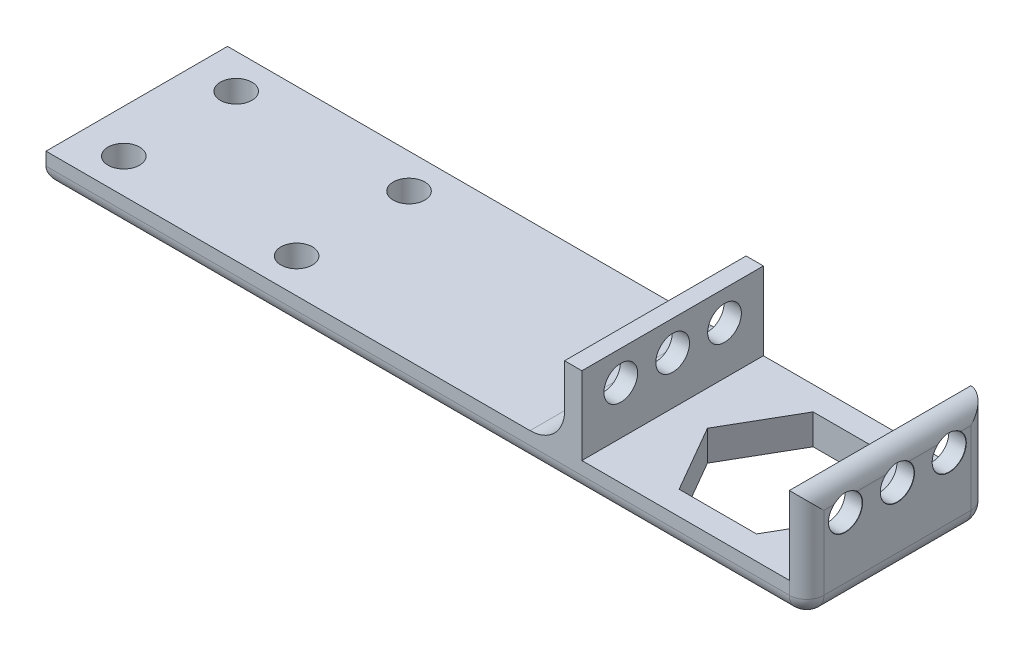
SolidWorks part; units mm, degrees
ref_plane "Front Plane" through (0, 0, 0) normal (0, 0, 1) x (1, 0, 0)
ref_plane "Top Plane" through (0, 0, 0) normal (0, 1, 0) x (1, 0, 0)
ref_plane "Right Plane" through (0, 0, 0) normal (1, 0, 0) x (0, 0, -1)
sketch "Sketch1" plane through (0, 0, 0) normal (0, 0, 1) x (1, 0, 0)
  line L1 (12, 5.0615) -> (12, -23.0615) construction
  line L2 (12, -20.5454) -> (14, -20.5454)
  line L3 (12, -20.5454) -> (12, -29.5454)
  line L5 (14, -20.5454) -> (14, -33.0454)
  line L6 (-12, -23.0615) -> (-12, 5.0615) construction
  line L7 (12, -29.5454) -> (-12, -29.5454)
  line L12 (-14, -29.5454) -> (-14, -20.5454)
  line L13 (-14, -20.5454) -> (-12, -20.5454)
  line L14 (-12, -29.5454) -> (-12, -20.5454)
  line L16 (14, -33.0454) -> (-74, -33.0454)
  line L18 (-14, -29.5454) -> (-74, -29.5454)
  line L19 (-74, -33.0454) -> (-74, -29.5454)
  dimension "D1" = 3.5
  dimension "D2" = 2
  dimension "D3" = 2
  dimension "D4" = 60
  dimension "D5" = 9
extrude "Boss-Extrude1" add sketch "Sketch1" against normal blind 21
fillet "Fillet1" radius 4 1 edges at (-14, -29.5454, -10.5)
hole_wizard "M3.5 Clearance Hole1" positions "Sketch2" profile "Sketch3" hole size "M3.5" standard "ANSI Metric" end condition through all
sketch "Sketch2" plane through (14, 0, 0) normal (1, 0, 0) x (0, 0, -1)
  arc A0 (2.5, -24) -> (6.5, -24) centre (4.5, -24) ccw construction
  arc A1 (2.5, -24) -> (6.5, -24) centre (4.5, -24) ccw construction
  arc A2 (8, -24) -> (13, -24) centre (10.5, -24) ccw construction
  arc A3 (8, -24) -> (13, -24) centre (10.5, -24) ccw construction
  arc A4 (8, -24) -> (13, -24) centre (10.5, -24) ccw construction
  arc A5 (8, -24) -> (13, -24) centre (10.5, -24) ccw construction
  arc A6 (14, -24) -> (19, -24) centre (16.5, -24) ccw construction
  arc A7 (14, -24) -> (19, -24) centre (16.5, -24) ccw construction
  point P0 (4.5, -24)
  point P2 (10.5, -24)
  point P4 (16.5, -24)
sketch "Sketch3" plane through (14, -24, -4.5) normal (0, 1, 0) x (0, 0, -1)
  line L0 (0, 0) -> (0, 88)
  line L1 (0, 88) -> (1.95, 88)
  line L2 (1.95, 88) -> (1.95, 0.025)
  line L3 (1.95, 0.025) -> (1.975, 0)
  line L5 (1.975, 0) -> (0, 0)
  line L6 (-1.95, 0.025) -> (-1.975, 0) construction
  line L11 (0, -6.35) -> (0, 107.95) construction
  dimension "Thru Hole Dia." = 3.9
  dimension "Thru Hole Depth" = 88
  dimension "Near C'Sink Dia." = 3.95
  dimension "Near C'Sink Angle" = 90
sketch "Sketch4" plane through (0, -33.0454, 0) normal (0, -1, 0) x (1, 0, 0)
  line L0 (14, -21) -> (14, 0) construction
  line L5 (-74, 0) -> (14, 0) construction
  line L6 (14, -10.5) -> (-74, -10.5) construction
  line L7 (-74, -21) -> (-74, 0) construction
  line L8 (-3.4992, -18.2528) -> (5.4529, -18.2528)
  line L9 (5.4529, -18.2528) -> (9.929, -10.5)
  line L10 (9.929, -10.5) -> (5.4529, -2.7472)
  line L11 (5.4529, -2.7472) -> (-3.4992, -2.7472)
  line L12 (-3.4992, -2.7472) -> (-7.9753, -10.5)
  line L13 (-7.9753, -10.5) -> (-3.4992, -18.2528)
  circle A0 centre (0.9769, -10.5) radius 7.7528 construction
  circle A1 centre (-69, -4) radius 1.825
  circle A2 centre (-49, -4) radius 1.825
  circle A3 centre (18.1662, -42.7784) radius 1.825
  circle A4 centre (28.1662, -60.0989) radius 1.825
  circle A5 centre (-69, -17) radius 1.825
  circle A6 centre (-49, -17) radius 1.825
  dimension "D1" = 3.65
  dimension "D2" = 4
  dimension "D3" = 5
  dimension "D4" = 2
extrude "Cut-Extrude1" cut sketch "Sketch4" against normal blind 21
fillet "Fillet3" radius 2 7 edges at (-74, -33.0454, -10.5) (-30, -33.0454, -21) (-30, -33.0454, 0) (14, -20.5454, -10.5) (14, -26.7954, -21) (14, -26.7954, 0) (14, -33.0454, -10.5)
